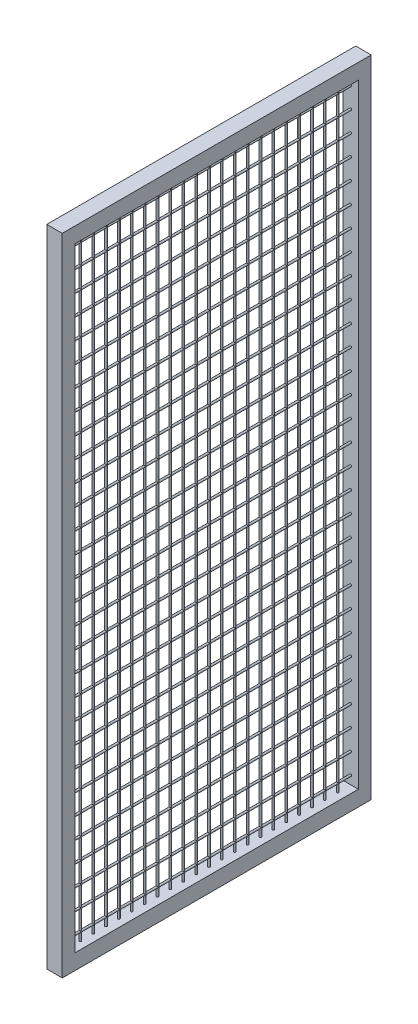
SolidWorks part; units mm, degrees
ref_plane "Piano frontale" through (0, 0, 0) normal (0, 0, 1) x (1, 0, 0)
ref_plane "Piano superiore" through (0, 0, 0) normal (0, 1, 0) x (1, 0, 0)
ref_plane "Piano destro" through (0, 0, 0) normal (1, 0, 0) x (0, 0, -1)
sketch "Schizzo1" plane through (0, 0, 1950) normal (0, 0, -1) x (-1, 0, 0)
  line L0 (-50, 2555) -> (-50, 50) construction
  line L1 (-30, 110) -> (30, 110)
  line L2 (-30, 110) -> (-30, 50)
  line L3 (-30, 50) -> (30, 50)
  line L4 (30, 110) -> (30, 50)
  line L5 (50, 2555) -> (50, 50) construction
  line L6 (-100, 50) -> (100, 50) construction
  line L7 (50, 2555) -> (-50, 2555) construction
  line L8 (-30, 2555) -> (30, 2555)
  line L9 (-30, 2555) -> (-30, 2495)
  line L10 (-30, 2495) -> (30, 2495)
  line L11 (30, 2555) -> (30, 2495)
  circle A0 centre (0, 2462.5) radius 3.75
  circle A1 centre (0, 2382.5) radius 3.75
  circle A2 centre (0, 2302.5) radius 3.75
  circle A3 centre (0, 2222.5) radius 3.75
  circle A4 centre (0, 2142.5) radius 3.75
  circle A5 centre (0, 2062.5) radius 3.75
  circle A6 centre (0, 1982.5) radius 3.75
  circle A7 centre (0, 1902.5) radius 3.75
  circle A8 centre (0, 1822.5) radius 3.75
  circle A9 centre (0, 1742.5) radius 3.75
  circle A10 centre (0, 1662.5) radius 3.75
  circle A11 centre (0, 1582.5) radius 3.75
  circle A12 centre (0, 1502.5) radius 3.75
  circle A13 centre (0, 1422.5) radius 3.75
  circle A14 centre (0, 1342.5) radius 3.75
  circle A15 centre (0, 1262.5) radius 3.75
  circle A16 centre (0, 1182.5) radius 3.75
  circle A17 centre (0, 1102.5) radius 3.75
  circle A18 centre (0, 1022.5) radius 3.75
  circle A19 centre (0, 942.5) radius 3.75
  circle A20 centre (0, 862.5) radius 3.75
  circle A21 centre (0, 782.5) radius 3.75
  circle A22 centre (0, 702.5) radius 3.75
  circle A23 centre (0, 622.5) radius 3.75
  circle A24 centre (0, 542.5) radius 3.75
  circle A25 centre (0, 462.5) radius 3.75
  circle A26 centre (0, 382.5) radius 3.75
  circle A27 centre (0, 302.5) radius 3.75
  circle A28 centre (0, 222.5) radius 3.75
  circle A29 centre (0, 142.5) radius 3.75
  dimension "D8" = 7.5
  dimension "D1" = 20
  dimension "D2" = 20
  dimension "D3" = 0
  dimension "D4" = 60
  dimension "D5" = 60
  dimension "D6" = 20
  dimension "D7" = 60
  dimension "D10" = 32.5
  dimension "D9" = 30
extrude "Estrusione-Estrusione1" add sketch "Schizzo1" along normal blind 1200
sketch "Schizzo2" plane through (0, 110, 0) normal (0, 1, 0) x (1, 0, 0)
  line L1 (-30, -750) -> (30, -750)
  line L5 (30, -750) -> (30, -1950) construction
  line L6 (-30, -750) -> (-30, -800)
  line L11 (-30, -800) -> (30, -800)
  line L16 (-30, -750) -> (-30, -1950) construction
  line L17 (-30, -1950) -> (30, -1950)
  line L18 (-30, -1950) -> (-30, -1900)
  line L19 (-30, -1900) -> (30, -1900)
  line L20 (30, -1950) -> (30, -1900)
  line L21 (30, -800) -> (30, -750)
  line L22 (-30, -1950) -> (30, -1950) construction
  circle A44 centre (0, -1850) radius 3.75
  circle A45 centre (0, -1800) radius 3.75
  circle A46 centre (0, -1750) radius 3.75
  circle A47 centre (0, -1700) radius 3.75
  circle A48 centre (0, -1650) radius 3.75
  circle A49 centre (0, -1600) radius 3.75
  circle A50 centre (0, -1550) radius 3.75
  circle A51 centre (0, -1500) radius 3.75
  circle A52 centre (0, -1450) radius 3.75
  circle A53 centre (0, -1400) radius 3.75
  circle A54 centre (0, -1350) radius 3.75
  circle A55 centre (0, -1300) radius 3.75
  circle A56 centre (0, -1250) radius 3.75
  circle A57 centre (0, -1200) radius 3.75
  circle A58 centre (0, -1150) radius 3.75
  circle A59 centre (0, -1100) radius 3.75
  circle A60 centre (0, -1050) radius 3.75
  circle A61 centre (0, -1000) radius 3.75
  circle A62 centre (0, -950) radius 3.75
  circle A63 centre (0, -900) radius 3.75
  circle A64 centre (0, -850) radius 3.75
  dimension "D3" = 50
  dimension "D5" = 21
  dimension "D1" = 50
  dimension "D2" = 60
  dimension "D8" = 0
  dimension "D4" = 50
extrude "Estrusione-Estrusione2" add sketch "Schizzo2" along normal up to surface (2385 mm away) up to face at (0, 2495, 1350)
